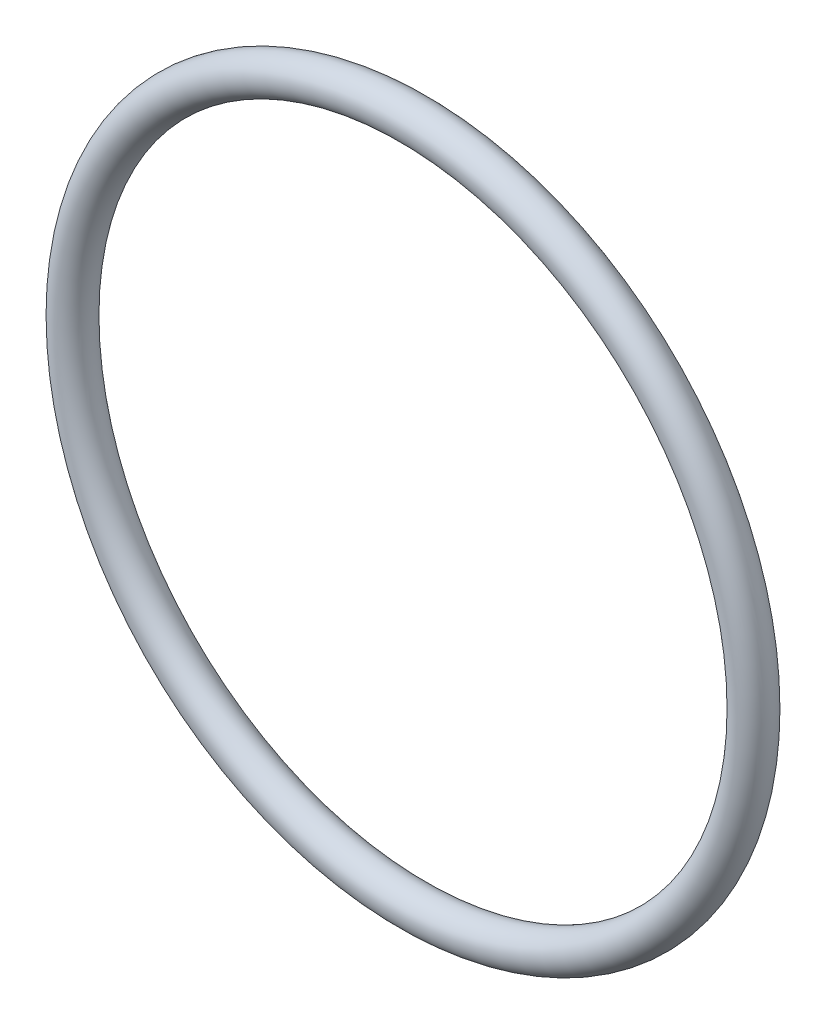
SolidWorks part; units mm, degrees
material "Rubber"
ref_plane "Front Plane" through (0, 0, 0) normal (0, 0, 1) x (1, 0, 0)
ref_plane "Top Plane" through (0, 0, 0) normal (0, 1, 0) x (1, 0, 0)
ref_plane "Right Plane" through (0, 0, 0) normal (1, 0, 0) x (0, 0, -1)
sketch "Sketch1" plane through (0, 0, 0) normal (0, 1, 0) x (1, 0, 0)
  line L0 (-0.635, 0) -> (23.749, 0)
  line L1 (11.557, 0) -> (11.557, 11.8878)
  circle A0 centre (0, 0) radius 0.635
  dimension "D1" = 1.27
  dimension "D2" = 24.384
revolve "Revolve1" add sketch "Sketch1" angle 360 about L1 region at (0, 0, -0.2695) region at (0, 0, 0.2695)
